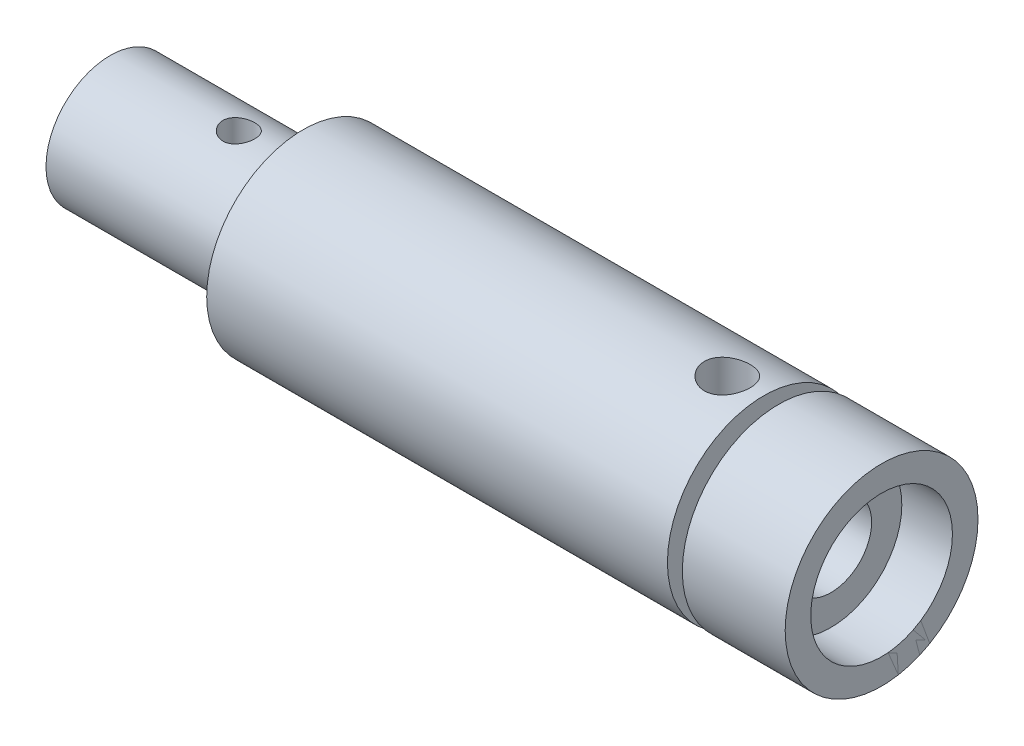
SolidWorks part; units mm, degrees
ref_plane "Front Plane" through (0, 0, 0) normal (0, 0, 1) x (1, 0, 0)
ref_plane "Top Plane" through (0, 0, 0) normal (0, 1, 0) x (1, 0, 0)
ref_plane "Right Plane" through (0, 0, 0) normal (1, 0, 0) x (0, 0, -1)
sketch "Sketch1" plane through (0, 0, 0) normal (1, 0, 0) x (0, 0, -1)
  circle A0 centre (0, 0) radius 4.7625
  dimension "D1" = 9.525
extrude "Boss-Extrude1" add sketch "Sketch1" along normal blind 38.1
sketch "Sketch2" plane through (38.1, 0, 0) normal (1, 0, 0) x (0, 0, -1)
  circle A0 centre (0, 0) radius 2.0066
extrude "Cut-Extrude1" cut sketch "Sketch2" against normal blind 10.414
sketch "Sketch3" plane through (0, 0, 0) normal (0, 1, 0) x (1, 0, 0)
  line L0 (38.1, -4.7625) -> (38.1, 4.7625) construction
  circle A0 centre (30.48, 0) radius 1.1303
  dimension "D1" = 7.62
extrude "Cut-Extrude2" cut sketch "Sketch3" along normal blind 8.6868
sketch "Sketch4" plane through (0, 0, 0) normal (-1, 0, 0) x (0, 0, 1)
  circle A0 centre (0, 0) radius 3.175
  circle A1 centre (0, 0) radius 5.0848
extrude "Cut-Extrude3" cut sketch "Sketch4" against normal blind 9.525
sketch "Sketch5" plane through (0, 0, 0) normal (0, 1, 0) x (1, 0, 0)
  line L0 (9.525, 4.7625) -> (9.525, -4.7625) construction
  circle A0 centre (6.35, 0) radius 0.7874
  dimension "D1" = 3.175
extrude "Cut-Extrude4" cut sketch "Sketch5" against normal through all and the other way through all
sketch "Sketch6" plane through (38.1, 0, 0) normal (1, 0, 0) x (0, 0, -1)
  circle A0 centre (0, 0) radius 3.5
  dimension "D1" = 7
extrude "Cut-Extrude5" cut sketch "Sketch6" against normal blind 2.5 contours A0
surface "Surface-Plane1"
ref_plane "Plane1" through (33.02, 0, 0) normal (1, 0, 0) x (0, 0, -1)
sketch "Sketch7" plane through (33.02, 0, 0) normal (1, 0, 0) x (0, 0, -1)
  circle A0 centre (0, 0) radius 4.7625
  circle A1 centre (0, 0) radius 2.667
  dimension "D1" = 5.334
extrude "Cut-Extrude7" cut sketch "Sketch7" against normal blind 0.7366
